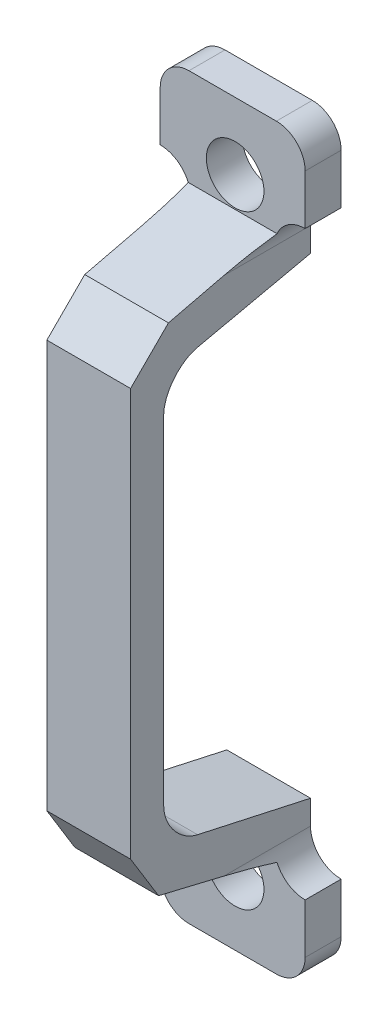
SolidWorks part; units mm, degrees
ref_plane "前视基准面" through (0, 0, 0) normal (0, 0, 1) x (1, 0, 0)
ref_plane "上视基准面" through (0, 0, 0) normal (0, 1, 0) x (1, 0, 0)
ref_plane "右视基准面" through (0, 0, 0) normal (1, 0, 0) x (0, 0, -1)
sketch "草图1" plane through (0, 0, 0) normal (0, 0, 1) x (1, 0, 0)
  line L1 (84.6239, -34.0071) -> (30.6239, -34.0071) construction
  line L2 (84.6239, -34.0071) -> (84.6239, -76.0071) construction
  line L3 (84.6239, -76.0071) -> (30.6239, -76.0071) construction
  line L7 (79.4177, -29.3519) -> (89.4859, -29.3519)
  line L8 (79.4177, -29.3519) -> (79.4177, -80.6623)
  line L9 (79.4177, -80.6623) -> (89.4859, -80.6623)
  line L10 (89.4859, -29.3519) -> (89.4859, -80.6623)
  circle A0 centre (84.6239, -34.0071) radius 2
  circle A3 centre (84.6239, -76.0071) radius 2
  point P0 (57.6239, -55.0071)
  point P9 (57.6239, -55.0071)
  dimension "D1" = 42
  dimension "D2" = 54
extrude "凸台-拉伸1" add sketch "草图1" along normal blind 2.5
sketch "草图2" plane through (89.4859, 0, 0) normal (1, 0, 0) x (0, 0, -1)
  line L0 (0, -55.0071) -> (-6.365, -55.0071) construction
  line L2 (-2.5, -80.6623) -> (-2.5, -29.3519) construction
  line L3 (11.4412, -36.0994) -> (-12.5931, -36.0994) construction
  line L4 (11.4412, -36.0994) -> (11.4412, -73.9148) construction
  line L5 (11.4412, -73.9148) -> (-12.5931, -73.9148) construction
  line L6 (-12.5931, -36.0994) -> (-12.5931, -73.9148) construction
  line L7 (11.4412, -36.0994) -> (-12.5931, -73.9148) construction
  line L8 (11.4412, -73.9148) -> (-12.5931, -36.0994) construction
  line L9 (-22.8373, -38.497) -> (-12.5, -38.497) construction
  line L10 (-22.8373, -38.497) -> (-22.8373, -71.5172) construction
  line L11 (-22.8373, -71.5172) -> (-12.5, -71.5172) construction
  line L12 (-12.5, -38.497) -> (-12.5, -71.5172) construction
  line L13 (-22.8373, -38.497) -> (-12.5, -71.5172) construction
  line L14 (-22.8373, -71.5172) -> (-12.5, -38.497) construction
  line L15 (-12.5, -71.5172) -> (-2.5, -73.9148)
  line L16 (-2.5, -73.9148) -> (-2.5, -36.0994)
  line L17 (-2.5, -36.0994) -> (-12.5, -38.497)
  line L18 (-12.5, -38.497) -> (-12.5, -71.5172)
  point P1 (-0.5759, -55.0071)
  point P7 (-17.6686, -55.0071)
  dimension "D1" = 10
extrude "凸台-拉伸2" add sketch "草图2" against normal up to surface (10.0682 mm away) up to face at (79.4177, -55.0071, 1.25)
sketch "草图3" plane through (89.4859, 0, 0) normal (1, 0, 0) x (0, 0, -1)
  line L0 (-14.5, -55.0071) -> (-17.2067, -55.0071) construction
  line L2 (0, -80.6623) -> (0, -29.3519) construction
  line L3 (-5.0776, -71.3953) -> (0, -71.3953) construction
  line L4 (-5.0776, -71.3953) -> (-5.0776, -38.6189) construction
  line L5 (-5.0776, -38.6189) -> (0, -38.6189) construction
  line L6 (0, -71.3953) -> (0, -38.6189) construction
  line L7 (-5.0776, -71.3953) -> (0, -38.6189) construction
  line L8 (-5.0776, -38.6189) -> (0, -71.3953) construction
  line L9 (-10.1988, -69.151) -> (0, -71.3953)
  line L10 (-13.2647, -40.8632) -> (-10.1988, -40.8632) construction
  line L11 (-13.2647, -40.8632) -> (-13.2647, -69.151) construction
  line L12 (-13.2647, -69.151) -> (-10.1988, -69.151) construction
  line L13 (-10.1988, -40.8632) -> (-10.1988, -69.151) construction
  line L14 (-13.2647, -40.8632) -> (-10.1988, -69.151) construction
  line L15 (-13.2647, -69.151) -> (-10.1988, -40.8632) construction
  line L16 (0, -71.3953) -> (0, -38.6189)
  line L17 (0, -38.6189) -> (-10.1988, -40.8632)
  line L18 (-10.1988, -40.8632) -> (-10.1988, -69.151)
  point P1 (-2.5388, -55.0071)
  point P9 (-11.7318, -55.0071)
extrude "切除-拉伸1" cut sketch "草图3" against normal through all both and the other way through all
sketch "草图4" plane through (0, 0, 12.5) normal (0, 0, 1) x (1, 0, 0)
  line L0 (84.4518, -40.8866) -> (84.4518, -50.8041) construction
  line L2 (79.4177, -55.0071) -> (74.8166, -55.0071) construction
  line L4 (79.4177, -36.9415) -> (79.4177, -73.0727) construction
  line L5 (79.4177, -71.5172) -> (79.4177, -38.497) construction
  line L6 (79.4177, -73.9148) -> (79.4177, -80.6623) construction
  line L7 (81.5444, -36.9415) -> (81.5444, -73.0727)
  line L8 (77.291, -36.9415) -> (77.291, -73.0727)
  line L9 (89.4859, -36.9415) -> (89.4859, -73.0727) construction
  line L10 (87.3592, -36.9415) -> (87.3592, -73.0727)
  line L11 (91.6126, -36.9415) -> (91.6126, -73.0727)
  arc A0 (81.5444, -36.9415) -> (77.291, -36.9415) centre (79.4177, -36.9415) ccw
  arc A1 (77.291, -73.0727) -> (81.5444, -73.0727) centre (79.4177, -73.0727) ccw
  arc A2 (87.3592, -36.9415) -> (91.6126, -36.9415) centre (89.4859, -36.9415) cw
  arc A3 (91.6126, -73.0727) -> (87.3592, -73.0727) centre (89.4859, -73.0727) cw
  point P10 (79.4177, -55.0071)
  point P17 (89.4859, -55.0071)
extrude "切除-拉伸2" cut sketch "草图4" against normal through all both and the other way through all
fillet "圆角1" radius 3 2 edges at (84.4518, -40.8632, 10.1988) (84.4518, -69.151, 10.1988)
fillet "圆角2" radius 2 4 edges at (89.4859, -80.6623, 1.25) (79.4177, -80.6623, 1.25) (89.4859, -29.3519, 1.25) (79.4177, -29.3519, 1.25)
chamfer "倒角2" distance 2 angle 45 2 edges at (84.4518, -38.497, 12.5) (84.4518, -71.5172, 12.5)
